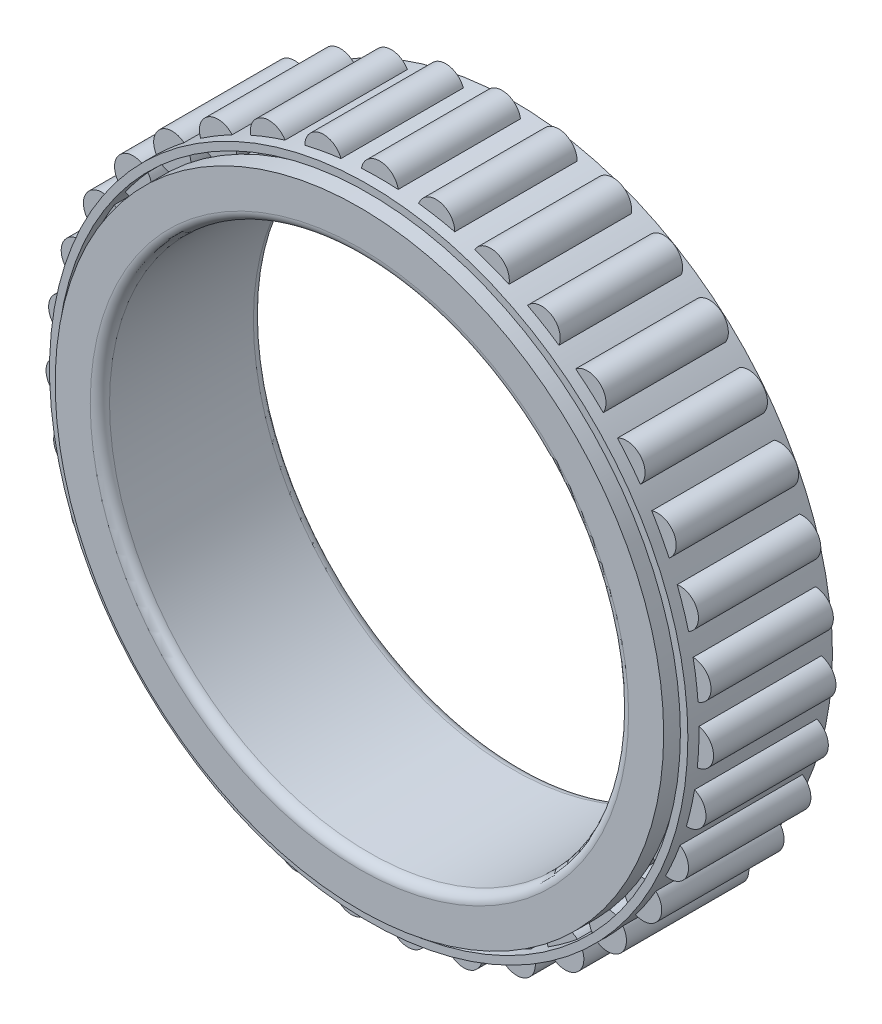
SolidWorks part; units mm, degrees
ref_plane "Front Plane" through (0, 0, 0) normal (0, 0, 1) x (1, 0, 0)
ref_plane "Top Plane" through (0, 0, 0) normal (0, 1, 0) x (1, 0, 0)
ref_plane "Right Plane" through (0, 0, 0) normal (1, 0, 0) x (0, 0, -1)
sketch "BaseSke" plane through (0, 0, 0) normal (1, 0, 0) x (0, 0, -1)
  line L0 (-42.3546, 0) -> (24.6132, 0) construction
  line L1 (-42.3546, 42.5375) -> (24.6132, 42.5375) construction
  line L2 (0, 129.5214) -> (0, -86.3012) construction
  line L3 (-8.25, 42.5375) -> (-8.25, 45.05) construction
  line L5 (-11, 35) -> (11, 35) construction
  line L6 (-8.25, 40.025) -> (8.25, 40.025)
  line L7 (-8.25, 40.025) -> (-8.25, 42.5375)
  line L8 (-8.25, 42.5375) -> (8.25, 42.5375)
  line L9 (8.25, 40.025) -> (8.25, 42.5375)
  line L10 (-8.25, 45.05) -> (8.25, 45.05) construction
  line L11 (8.25, 45.05) -> (8.25, 42.5375) construction
  line L12 (-8.25, 40.025) -> (-8.25, 35) construction
  line L13 (-8.25, 45.05) -> (-8.25, 40.025) construction
  dimension "D2" = 16.5
  dimension "Bearing_Outside_Diameter" = 90.1
  dimension "Bearing_Thickness" = 22
revolve "Roller" add sketch "BaseSke" angle 360 about L8
sketch "OuterRaceSke" plane through (0, 0, 0) normal (1, 0, 0) x (0, 0, -1)
  line L0 (0, 0) -> (0, 87.5396) construction
  line L1 (-11, 35) -> (11, 35)
  line L2 (-11, 35) -> (-11, 41.03)
  line L3 (-11, 41.03) -> (-8.275, 41.03)
  line L4 (11, 35) -> (11, 41.03)
  line L5 (-50.3916, 0) -> (55.2197, 0) construction
  line L7 (8.275, 41.03) -> (11, 41.03)
  line L8 (-8.25, 40.025) -> (8.25, 40.025) construction
  line L9 (-8.275, 41.03) -> (-8.275, 40.045)
  line L10 (-8.275, 40.045) -> (8.275, 40.045)
  line L11 (8.275, 41.03) -> (8.275, 40.045)
  dimension "D2" = 82.06
  dimension "D1" = 16.55
  dimension "D3" = 0.02
revolve "OuterRace" add sketch "OuterRaceSke" angle 360 about L5
sketch "CageSke" plane through (0, 0, 0) normal (1, 0, 0) x (0, 0, -1)
  line L0 (-70.8626, 0) -> (113.5527, 0) construction
  line L1 (0, 58.441) -> (0, -70.8113) construction
  line L2 (-9.75, 42.035) -> (9.75, 42.035)
  line L3 (-9.75, 42.035) -> (-9.75, 43.04)
  line L4 (-33.2996, 42.5375) -> (13.017, 42.5375) construction
  line L5 (-42.3546, 42.5375) -> (24.6132, 42.5375) construction
  line L6 (0, 129.5214) -> (0, -86.3012) construction
  line L7 (-9.75, 43.04) -> (9.75, 43.04)
  line L9 (9.75, 42.035) -> (9.75, 43.04)
  point P17 (0, 42.035)
  dimension "D1" = 19.5
  dimension "D2" = 1.005
revolve "Cage" add sketch "CageSke" angle 360 about L0
fillet "Fillet1" radius 1.3 2 edges at (35, 0, -11) (35, 0, 11)
pattern_circular "CirPatternBall" count 35 over 360 about axis through (0, 0, 50.3916) along (0, 0, -1) of "Roller"
sketch "SimplifiedSke" plane through (0, 0, 0) normal (1, 0, 0) x (0, 0, -1)
  line L0 (37.5911, 0) -> (-37.5911, 0) construction
  line L1 (-13.1351, 42.5375) -> (13.151, 42.5375) construction
  line L2 (-8.25, 45.05) -> (8.25, 45.05)
  line L3 (-8.25, 45.05) -> (-8.25, 40.025)
  line L4 (-8.25, 40.025) -> (8.25, 40.025)
  line L5 (8.25, 45.05) -> (8.25, 40.025)
  line L6 (-42.3546, 42.5375) -> (24.6132, 42.5375) construction
revolve "Simplified" [suppressed] add sketch "SimplifiedSke" angle 360 about L0
equation "\"D2@BaseSke\" = \"Bearing_Thickness@BaseSke\"*0.75"
equation "\"D1@OuterRaceSke\" = \"Bearing_Thickness@BaseSke\"*0.75+0.05"
equation "\"D1@CageSke\" = \"Bearing_Thickness@BaseSke\"*0.75+3"
equation "\"D2@OuterRaceSke\" = \"Bearing_Outside_Diameter@BaseSke\" -  ( \"Bearing_Outside_Diameter@BaseSke\" - \"Bearing_Inside_Diameter@BaseSke\" )  * 0.4"
equation "\"D2@CageSke\" =  ( \"Bearing_Outside_Diameter@BaseSke\" - \"Bearing_Inside_Diameter@BaseSke\" )  / 20"
equation "\"D1@CirPatternBall\" =  int( \"Bearing_Outside_Diameter@BaseSke\" *  pi  /  ( \"Bearing_Outside_Diameter@BaseSke\" - \"Bearing_Inside_Diameter@BaseSke\" )  * 2.5 ) "
